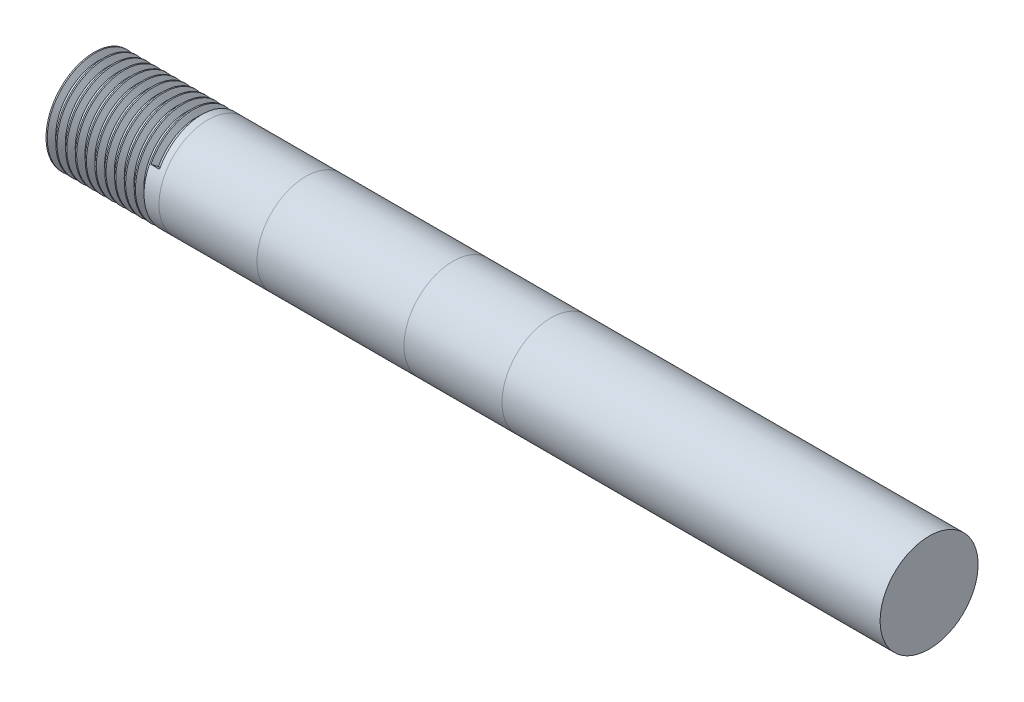
SolidWorks part; units mm, degrees
ref_plane "Front Plane" through (0, 0, 0) normal (0, 0, 1) x (1, 0, 0)
ref_plane "Top Plane" through (0, 0, 0) normal (0, 1, 0) x (1, 0, 0)
ref_plane "Right Plane" through (0, 0, 0) normal (1, 0, 0) x (0, 0, -1)
sketch "Sketch1" plane through (0, 0, 0) normal (0, 0, 1) x (1, 0, 0)
  line L0 (0, 0) -> (0, 6.35)
  line L1 (0, 6.35) -> (108.5625, 6.35)
  line L4 (108.5625, 6.35) -> (108.5625, 0)
  line L5 (108.5625, 0) -> (0, 0)
  line L6 (-315.9627, 0) -> (15482.1706, 0) construction
  dimension "D1" = 12.7
  dimension "D3" = 108.5625
revolve "Revolve1" add sketch "Sketch1" angle 360 about L6
thread "Thread1" pitch 1.27 method cut profile "Thread Profile1" start angle 0, offset 1.27, length 14.5, pitch 1.27, diameter 12.7
ref_plane "Plane1" through (-1.27, 0, -6.35) normal (0, -1, 0) x (0, 0, -1)
sketch "Thread Profile1" plane through (-1.27, 0, -6.35) normal (0, -1, 0) x (0, 0, -1)
  line L0 (0, 0) -> (0, 1.27) construction
  line L11 (0, 0) -> (0, 1.1112)
  line L12 (0, 1.1112) -> (-0.6874, 0.7144)
  line L13 (-0.6874, 0.7144) -> (-0.6874, 0.3969)
  line L15 (-0.6874, 0.3969) -> (0, 0)
  line L17 (-0.6874, 0.5556) -> (0, 0.5556) construction
  point P2 (0, 0)
  dimension "Pitch" = 1.27
  dimension "Profile_Angle" = 60
  dimension "Profile_Land" = 0.3175
  dimension "Profile_Height" = 0.6874
sketch "Sketch2" plane through (0, 0, 0) normal (0, 0, 1) x (1, 0, 0)
  line L0 (59.5625, 6.35) -> (59.5625, -6.35)
  line L1 (108.5625, 6.35) -> (14.1288, 6.35) construction
  line L2 (13.4938, -6.35) -> (108.5625, -6.35) construction
  line L3 (46.8625, 6.35) -> (46.8625, -6.35)
  line L4 (27.8125, 6.35) -> (27.8125, -6.35)
  line L5 (15.1125, 6.35) -> (15.1125, -6.35)
  line L6 (108.5625, -6.35) -> (108.5625, 6.35) construction
  dimension "D1" = 49
  dimension "D2" = 12.7
  dimension "D3" = 12.7
  dimension "D4" = 19.05
split line "Split Line1"
